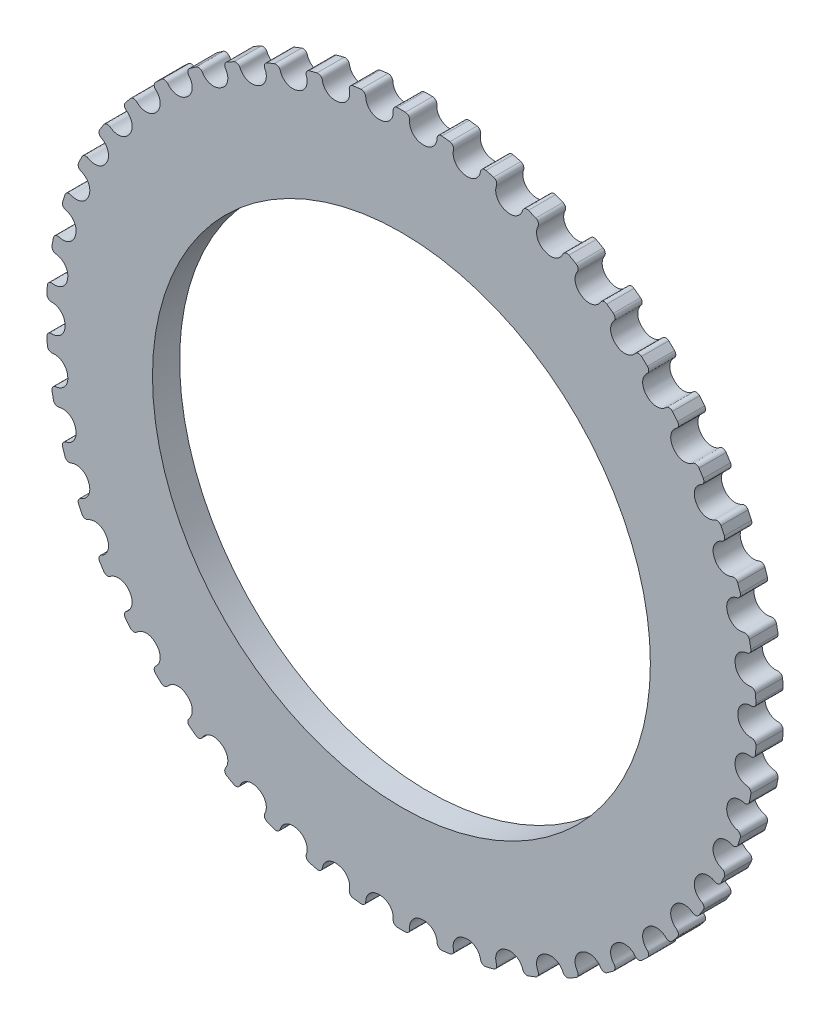
SolidWorks part; units mm, degrees
ref_plane "Front Plane" through (0, 0, 0) normal (0, 0, 1) x (1, 0, 0)
ref_plane "Top Plane" through (0, 0, 0) normal (0, 1, 0) x (1, 0, 0)
ref_plane "Right Plane" through (0, 0, 0) normal (1, 0, 0) x (0, 0, -1)
ref_axis "Axis1" through (0, 0, 55) along (0, 0, -1)
sketch "SketchRevolveGearBelt01" plane through (0, 0, 0) normal (1, 0, 0) x (0, 0, -1)
  line L0 (0, 0) -> (1, 0) construction
  line L1 (1.5, 0) -> (1.5, 39.2172)
  line L2 (1.5, 39.2172) -> (-1.5, 39.2172)
  line L3 (-1.5, 39.2172) -> (-1.5, 0)
  line L4 (-1.5, 0) -> (1.5, 0)
  dimension "GearBeltSide1" = 1.5
  dimension "GearBeltOutsideDiameter" = 39.2172
  dimension "GearBeltSide2" = 1.5
revolve "GearBelt01" add sketch "SketchRevolveGearBelt01" angle 360 about L0
sketch "SketchToothGearBelt01" plane through (0, 0, 0) normal (0, 0, 1) x (1, 0, 0)
  arc A0 (39.1647, 2.0323) -> (39.1647, -2.0323) centre (0, 0) cw
  spline S0 degree 3 poles (39.1647, -2.0323) (39.166, -2.006) (39.1649, -1.9663) (39.1569, -1.9141) (39.1478, -1.8755) (39.1356, -1.8378) (39.1204, -1.8013) (39.1023, -1.7661) (39.0814, -1.7324) (39.0578, -1.7006) (39.0317, -1.6708) (39.0033, -1.6432) (38.9728, -1.618) (38.9403, -1.5953) (38.9061, -1.5754) (38.8703, -1.5582) (38.8333, -1.5441) (38.7953, -1.533) (38.7565, -1.525) (38.7172, -1.5201) (38.6658, -1.5185) (38.59, -1.5198) (38.4897, -1.516) (38.3775, -1.5026) (38.2667, -1.4805) (38.158, -1.4498) (38.052, -1.4107) (37.9494, -1.3633) (37.8509, -1.3081) (37.7569, -1.2453) (37.6682, -1.1753) (37.5853, -1.0986) (37.5086, -1.0156) (37.4387, -0.9268) (37.376, -0.8329) (37.3208, -0.7343) (37.2735, -0.6317) (37.2344, -0.5257) (37.2037, -0.4169) (37.1817, -0.3061) (37.1683, -0.1939) (37.1652, -0.1051) (37.1655, -0.0405) (37.1655, 0) (37.1655, 0.0405) (37.1652, 0.1051) (37.1683, 0.1939) (37.1817, 0.3061) (37.2037, 0.4169) (37.2344, 0.5257) (37.2735, 0.6317) (37.3208, 0.7343) (37.376, 0.8329) (37.4387, 0.9268) (37.5086, 1.0156) (37.5853, 1.0986) (37.6682, 1.1753) (37.7569, 1.2453) (37.8509, 1.3081) (37.9494, 1.3633) (38.052, 1.4107) (38.158, 1.4498) (38.2667, 1.4805) (38.3775, 1.5026) (38.4897, 1.516) (38.59, 1.5198) (38.6658, 1.5185) (38.7172, 1.5201) (38.7565, 1.525) (38.7953, 1.533) (38.8333, 1.5441) (38.8703, 1.5582) (38.9061, 1.5754) (38.9403, 1.5953) (38.9728, 1.618) (39.0033, 1.6432) (39.0317, 1.6708) (39.0578, 1.7006) (39.0814, 1.7324) (39.1023, 1.7661) (39.1204, 1.8013) (39.1356, 1.8378) (39.1478, 1.8755) (39.1569, 1.9141) (39.1649, 1.9663) (39.166, 2.006) (39.1647, 2.0323) knots 0 0 0 0 0.012346 0.01852 0.024693 0.030866 0.037039 0.043212 0.049386 0.055559 0.061732 0.067905 0.074078 0.080252 0.086425 0.092598 0.098771 0.104944 0.111118 0.117291 0.123464 0.135171 0.152781 0.17039 0.188 0.205609 0.223219 0.240828 0.258438 0.276048 0.293657 0.311267 0.328876 0.346486 0.364095 0.381705 0.399315 0.416924 0.434534 0.452143 0.469753 0.487362 0.493681 0.5 0.506319 0.512638 0.530247 0.547857 0.565466 0.583076 0.600685 0.618295 0.635905 0.653514 0.671124 0.688733 0.706343 0.723952 0.741562 0.759172 0.776781 0.794391 0.812 0.82961 0.847219 0.864829 0.876536 0.882709 0.888882 0.895056 0.901229 0.907402 0.913575 0.919748 0.925922 0.932095 0.938268 0.944441 0.950614 0.956788 0.962961 0.969134 0.975307 0.98148 0.987654 1 1 1 1
extrude "ToothExtrudeCutGearBelt01" cut sketch "SketchToothGearBelt01" against normal blind 7.239 and the other way blind 7.239
pattern_circular "PatternGearBelt01" count 50 every 7.2 about axis through (0, 0, 55) along (0, 0, -1) of "ToothExtrudeCutGearBelt01"
sketch "BoreRevolveSketch" plane through (0, 0, 0) normal (1, 0, 0) x (0, 0, -1)
  line L0 (0, 0) -> (1, 0) construction
  line L1 (-7.239, 0) -> (7.239, 0)
  line L2 (7.239, 0) -> (7.239, 27.5)
  line L3 (7.239, 27.5) -> (-7.239, 27.5)
  line L4 (-7.239, 27.5) -> (-7.239, 0)
  dimension "BoreSide1" = 7.239
  dimension "TaperSide1" = 27.5
  dimension "BoreSide2" = 7.239
  dimension "TaperSide2" = 27.5
revolve "BoreRevolveCut" cut sketch "BoreRevolveSketch" angle 360 about L0
sketch "AuxiliarySketchGearBelt01" plane through (0, 0, 0) normal (0, 0, 1) x (1, 0, 0)
  circle A0 centre (0, 0) radius 39.7887 construction
  dimension "PitchDiameter" = 79.5774
